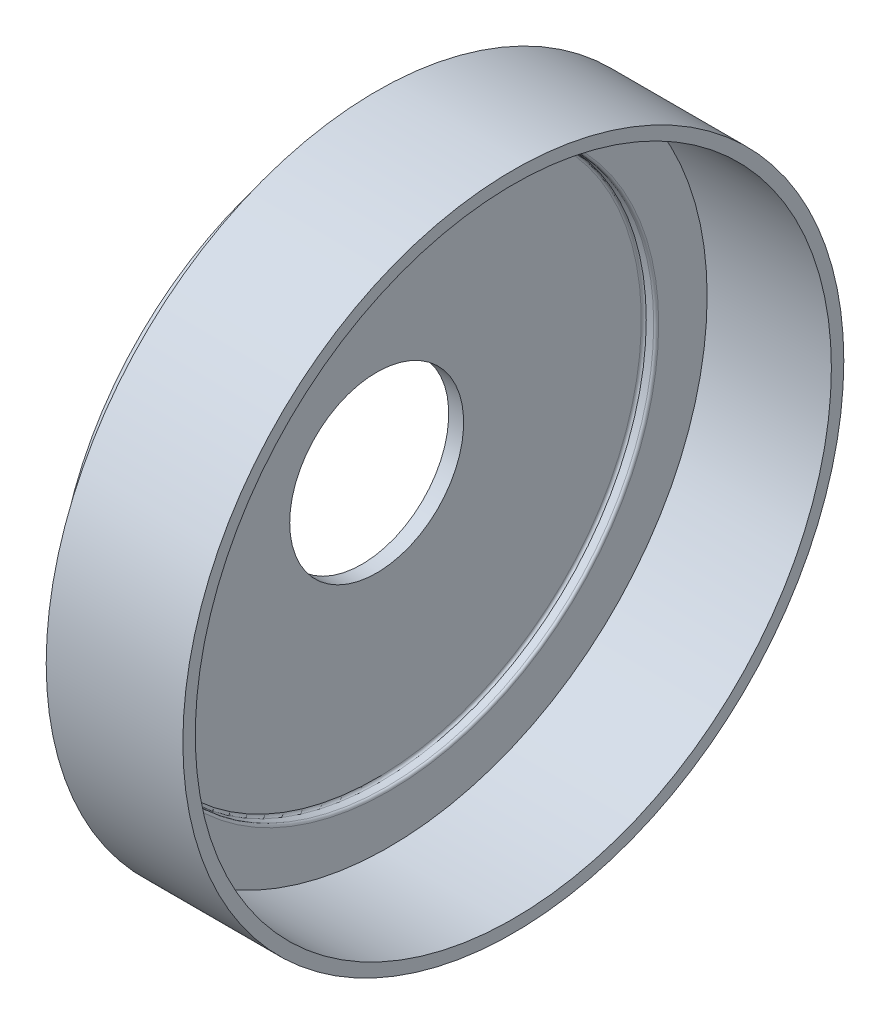
SolidWorks part; units mm, degrees
ref_plane "Front Plane" through (0, 0, 0) normal (1, 0, 0) x (0, 1, 0)
ref_plane "Top Plane" through (0, 0, 0) normal (0, 0, 1) x (0, 1, 0)
ref_plane "Right Plane" through (0, 0, 0) normal (0, 1, 0) x (-1, 0, 0)
sketch "Sketch1" plane through (0, 0, 0) normal (1, 0, 0) x (0, 1, 0)
  circle A0 centre (0, 0) radius 25.6
  circle A1 centre (0, 0) radius 26.6
  dimension "D1" = 51.2
  dimension "D2" = 1
extrude "Boss-Extrude1" add sketch "Sketch1" along normal blind 10
sketch "Sketch2" plane through (0, 0, 0) normal (-1, 0, 0) x (0, -1, 0)
  circle A0 centre (0, 0) radius 26.6
  circle A1 centre (0, 0) radius 26.6 construction
  circle A2 centre (0, 0) radius 21.5
  dimension "D1" = 43
extrude "Boss-Extrude2" add sketch "Sketch2" along normal blind 1
sketch "Sketch3" plane through (-1, 0, 0) normal (-1, 0, 0) x (0, -1, 0)
  circle A0 centre (0, 0) radius 23
  dimension "D1" = 46
extrude "Boss-Extrude3" add sketch "Sketch3" along normal blind 1.2
sketch "Sketch4" plane through (-2.2, 0, 0) normal (-1, 0, 0) x (0, -1, 0)
  circle A0 centre (0, 0) radius 22
  circle A1 centre (0, 0) radius 23
  circle A2 centre (0, 0) radius 23 construction
  dimension "D1" = 1
extrude "Boss-Extrude4" add sketch "Sketch4" along normal blind 1.6
sketch "Sketch5" plane through (-2.2, 0, 0) normal (-1, 0, 0) x (0, -1, 0)
  circle A0 centre (0, 0) radius 7
  dimension "D1" = 14
extrude "Cut-Extrude1" cut sketch "Sketch5" against normal up to surface (1.2 mm away) up to face at (-1, 0, 21.5)
fillet "Fillet1" radius 0.2 2 edges at (-1, 0, 21.5) (0, 0, 21.5)
fillet "Fillet2" radius 0.4 1 edges at (-2.2, 0, 22)
